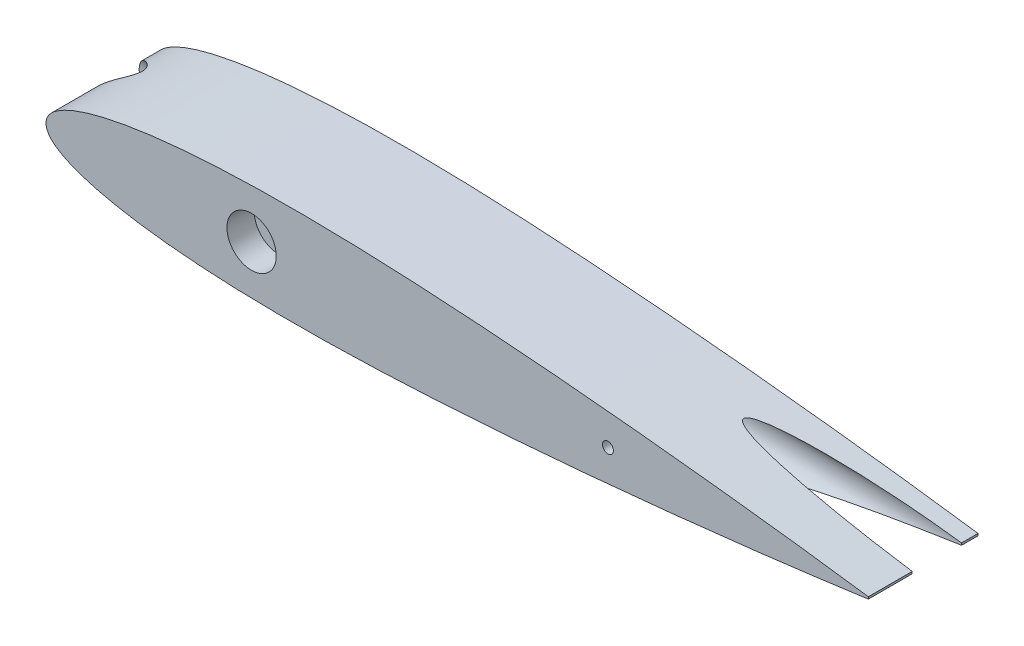
SolidWorks part; units mm, degrees
material "ABS"
ref_plane "Front Plane" through (0, 0, 0) normal (0, 0, 1) x (1, 0, 0)
ref_plane "Top Plane" through (0, 0, 0) normal (0, 1, 0) x (1, 0, 0)
ref_plane "Right Plane" through (0, 0, 0) normal (1, 0, 0) x (0, 0, -1)
sketch "Sketch5" plane through (0, 0, 0) normal (0, 0, 1) x (1, 0, 0)
  line L1 (300, 0.378) -> (300, -0.378)
  spline S1 degree 3 poles (300, 0.378) (299.2704, 0.4794) (297.2347, 0.7625) (293.6597, 1.2577) (289.1124, 1.8742) (284.0808, 2.5445) (278.752, 3.2381) (273.2659, 3.9349) (267.706, 4.629) (262.1146, 5.3131) (256.5083, 5.9822) (250.8917, 6.638) (245.2696, 7.2818) (239.6473, 7.9122) (234.0251, 8.527) (228.3991, 9.1262) (222.7683, 9.7131) (217.1359, 10.2875) (211.5054, 10.8469) (205.8776, 11.3916) (200.2515, 11.9209) (194.6264, 12.4346) (189.0028, 12.9319) (183.3815, 13.4131) (177.7632, 13.8764) (172.1483, 14.3212) (166.5375, 14.7478) (160.9317, 15.1542) (155.3317, 15.5391) (149.7375, 15.9026) (144.1487, 16.2418) (138.5657, 16.5574) (132.9909, 16.8474) (127.4274, 17.1102) (121.8776, 17.3439) (116.3408, 17.5453) (110.8155, 17.7127) (105.3013, 17.8445) (99.8006, 17.9401) (94.3174, 17.9966) (88.8558, 18.0101) (83.4186, 17.9792) (78.0085, 17.8992) (72.6285, 17.767) (67.2827, 17.5794) (61.9774, 17.3315) (56.7207, 17.021) (51.5252, 16.641) (46.4082, 16.1902) (41.3942, 15.6617) (36.5157, 15.054) (31.819, 14.3656) (27.3662, 13.6035) (23.2352, 12.7826) (19.5026, 11.9203) (16.2183, 11.0446) (13.3892, 10.1751) (10.9849, 9.3335) (8.9616, 8.5221) (7.2673, 7.747) (5.8461, 7.0106) (4.6477, 6.3006) (3.6282, 5.6065) (2.7519, 4.9266) (2.0063, 4.2499) (1.3906, 3.5703) (0.901, 2.8909) (0.5293, 2.2202) (0.2605, 1.5665) (0.0857, 0.931) (-0.0035, 0.309) (-0.0035, -0.309) (0.0857, -0.931) (0.2605, -1.5665) (0.5293, -2.2202) (0.901, -2.8909) (1.3906, -3.5703) (2.0063, -4.2499) (2.7519, -4.9266) (3.6282, -5.6065) (4.6477, -6.3006) (5.8461, -7.0106) (7.2673, -7.747) (8.9616, -8.5221) (10.9849, -9.3335) (13.3892, -10.1751) (16.2183, -11.0446) (19.5026, -11.9203) (23.2352, -12.7826) (27.3661, -13.6036) (31.8191, -14.3651) (36.5156, -15.0541) (41.3942, -15.6616) (46.4082, -16.1902) (51.5252, -16.641) (56.7207, -17.021) (61.9774, -17.3315) (67.2827, -17.5794) (72.6285, -17.767) (78.0085, -17.8992) (83.4186, -17.9792) (88.8558, -18.0101) (94.3174, -17.9966) (99.8006, -17.9401) (105.3013, -17.8445) (110.8155, -17.7127) (116.3408, -17.5453) (121.8776, -17.3439) (127.4274, -17.1102) (132.9909, -16.8474) (138.5657, -16.5574) (144.1487, -16.2418) (149.7375, -15.9026) (155.3317, -15.5391) (160.9317, -15.1542) (166.5375, -14.7478) (172.1483, -14.3212) (177.7632, -13.8764) (183.3815, -13.4131) (189.0028, -12.9319) (194.6264, -12.4346) (200.2515, -11.9209) (205.8776, -11.3916) (211.5054, -10.8469) (217.1359, -10.2875) (222.7683, -9.7131) (228.3991, -9.1262) (234.0251, -8.527) (239.6473, -7.9122) (245.2696, -7.2818) (250.8917, -6.638) (256.5083, -5.9822) (262.1146, -5.3131) (267.706, -4.629) (273.2659, -3.9349) (278.752, -3.2381) (284.0808, -2.5445) (289.1124, -1.8742) (293.6597, -1.2577) (297.2347, -0.7625) (299.2704, -0.4794) (300, -0.378) knots 0 0 0 0 0.003612 0.010079 0.017699 0.026115 0.034971 0.04405 0.053234 0.062448 0.071674 0.080921 0.090178 0.099424 0.108664 0.117912 0.12717 0.136427 0.145675 0.154916 0.164153 0.173387 0.182616 0.191838 0.201053 0.21026 0.219459 0.228647 0.237822 0.246985 0.256137 0.265279 0.274407 0.283512 0.292592 0.301646 0.310682 0.319699 0.328695 0.33766 0.346589 0.355477 0.364323 0.373122 0.381868 0.390553 0.399166 0.40769 0.416098 0.424355 0.432412 0.440205 0.447631 0.454564 0.460855 0.466413 0.471229 0.475366 0.478901 0.481915 0.484499 0.486747 0.488741 0.490543 0.492182 0.493673 0.495032 0.496279 0.497425 0.49849 0.499503 0.500497 0.50151 0.502575 0.503721 0.504968 0.506327 0.507818 0.509457 0.511259 0.513253 0.515501 0.518085 0.521099 0.524634 0.528771 0.533587 0.539145 0.545436 0.55237 0.559795 0.567588 0.575645 0.583902 0.59231 0.600834 0.609447 0.618132 0.626878 0.635677 0.644523 0.653411 0.66234 0.671305 0.680301 0.689318 0.698354 0.707408 0.716488 0.725593 0.734721 0.743863 0.753015 0.762178 0.771353 0.780541 0.78974 0.798947 0.808162 0.817384 0.826613 0.835847 0.845084 0.854325 0.863573 0.87283 0.882088 0.891336 0.900576 0.909822 0.919079 0.928326 0.937552 0.946766 0.95595 0.965029 0.973885 0.982301 0.989921 0.996388 1 1 1 1
  dimension "Tail chord" = 300
extrude "Boss-Extrude1" add sketch "Sketch5" along normal blind 40
sketch "Sketch6" plane through (0, 0, 0) normal (1, 0, 0) x (0, 0, -1)
  line L0 (0, -18.0036) -> (0, 18.0036) construction
  circle A0 centre (-15, 0) radius 9
  dimension "D1" = 15
  dimension "D2" = 18
extrude "Cut-Extrude6" cut sketch "Sketch6" against normal through all both and the other way through all
ref_plane "Plane1" through (0, 0, 40) normal (0, 0, 1) x (1, 0, 0)
sketch "Sketch7" plane through (0, 0, 40) normal (0, 0, 1) x (1, 0, 0)
  circle A0 centre (75, 0) radius 9
  circle A1 centre (205, 0) radius 2
  dimension "D3" = 18
  dimension "D4" = 4
  dimension "Tail chord qtr" = 75
  dimension "Small hole" = 130
extrude "Cut-Extrude7" cut sketch "Sketch7" against normal blind 10
curve "Curve6"
  spline degree 3 poles (298.242, -0.1932, 0) (300.4407, 0, 0) (298.242, 0.1932, 0) (296.4349, 0.5367, 0) (292.0253, 1.0976, 0) (286.5771, 1.8592, 0) (279.4156, 2.8001, 0) (270.9173, 3.8949, 0) (261.066, 5.1159, 0) (250.0071, 6.4339, 0) (237.8495, 7.8187, 0) (224.7304, 9.2395, 0) (210.7923, 10.6647, 0) (196.1883, 12.0613, 0) (181.0783, 13.3946, 0) (165.6277, 14.6278, 0) (150.0058, 15.7225, 0) (134.3834, 16.6392, 0) (118.9317, 17.3387, 0) (103.8195, 17.7845, 0) (89.2123, 17.9443, 0) (75.2698, 17.7935, 0) (62.1444, 17.3161, 0) (49.9793, 16.5075, 0) (38.907, 15.374, 0) (29.0471, 13.9333, 0) (20.5034, 12.2128, 0) (13.3641, 10.246, 0) (7.6828, 8.0707, 0) (3.4992, 5.7028, 0) (0.7348, 3.1014, 0) (-0.3264, 0, 0) (0.7348, -3.1014, 0) (3.4992, -5.7028, 0) (7.6828, -8.0707, 0) (13.3641, -10.246, 0) (20.5034, -12.2128, 0) (29.0471, -13.9333, 0) (38.907, -15.374, 0) (49.9793, -16.5075, 0) (62.1444, -17.3161, 0) (75.2698, -17.7935, 0) (89.2123, -17.9443, 0) (103.8195, -17.7845, 0) (118.9317, -17.3387, 0) (134.3834, -16.6392, 0) (150.0058, -15.7225, 0) (165.6277, -14.6278, 0) (181.0783, -13.3946, 0) (196.1883, -12.0613, 0) (210.7923, -10.6647, 0) (224.7304, -9.2395, 0) (237.8495, -7.8187, 0) (250.0071, -6.4339, 0) (261.066, -5.1159, 0) (270.9173, -3.8949, 0) (279.4156, -2.8001, 0) (286.5771, -1.8592, 0) (292.0253, -1.0976, 0) (296.4349, -0.5367, 0) (298.242, -0.1932, 0) (300.4407, 0, 0) (298.242, 0.1932, 0) knots -0.012119 -0.005412 -0.001357 0 0.001357 0.005412 0.012119 0.021403 0.033159 0.047255 0.063534 0.081814 0.101892 0.123547 0.146538 0.170613 0.195504 0.220938 0.246636 0.272314 0.297694 0.3225 0.346466 0.36934 0.390884 0.410879 0.429129 0.445462 0.459736 0.471848 0.481751 0.489494 0.495334 0.5 0.504666 0.510506 0.518249 0.528152 0.540264 0.554538 0.570871 0.589121 0.609116 0.63066 0.653534 0.6775 0.702306 0.727686 0.753364 0.779062 0.804496 0.829387 0.853462 0.876453 0.898108 0.918186 0.936466 0.952745 0.966841 0.978597 0.987881 0.994588 0.998643 1 1.001357 1.005412 1.012119 periodic
sketch "Sketch8" plane through (0, 0, 0) normal (0, 0, 1) x (1, 0, 0)
  spline S0 degree 3 poles (298.242, -0.1932) (300.4407, 0) (298.242, 0.1932) (296.4349, 0.5367) (292.0253, 1.0976) (286.5771, 1.8592) (279.4156, 2.8001) (270.9173, 3.8949) (261.066, 5.1159) (250.0071, 6.4339) (237.8495, 7.8187) (224.7304, 9.2395) (210.7923, 10.6647) (196.1883, 12.0613) (181.0783, 13.3946) (165.6277, 14.6278) (150.0058, 15.7225) (134.3834, 16.6392) (118.9317, 17.3387) (103.8195, 17.7845) (89.2123, 17.9443) (75.2698, 17.7935) (62.1444, 17.3161) (49.9793, 16.5075) (38.907, 15.374) (29.0471, 13.9333) (20.5034, 12.2128) (13.3641, 10.246) (7.6828, 8.0707) (3.4992, 5.7028) (0.7348, 3.1014) (-0.3264, 0) (0.7348, -3.1014) (3.4992, -5.7028) (7.6828, -8.0707) (13.3641, -10.246) (20.5034, -12.2128) (29.0471, -13.9333) (38.907, -15.374) (49.9793, -16.5075) (62.1444, -17.3161) (75.2698, -17.7935) (89.2123, -17.9443) (103.8195, -17.7845) (118.9317, -17.3387) (134.3834, -16.6392) (150.0058, -15.7225) (165.6277, -14.6278) (181.0783, -13.3946) (196.1883, -12.0613) (210.7923, -10.6647) (224.7304, -9.2395) (237.8495, -7.8187) (250.0071, -6.4339) (261.066, -5.1159) (270.9173, -3.8949) (279.4156, -2.8001) (286.5771, -1.8592) (292.0253, -1.0976) (296.4349, -0.5367) (298.242, -0.1932) (300.4407, 0) (298.242, 0.1932) knots -0.012119 -0.005412 -0.001357 0 0.001357 0.005412 0.012119 0.021403 0.033159 0.047255 0.063534 0.081814 0.101892 0.123547 0.146538 0.170613 0.195504 0.220938 0.246636 0.272314 0.297694 0.3225 0.346466 0.36934 0.390884 0.410879 0.429129 0.445462 0.459736 0.471848 0.481751 0.489494 0.495334 0.5 0.504666 0.510506 0.518249 0.528152 0.540264 0.554538 0.570871 0.589121 0.609116 0.63066 0.653534 0.6775 0.702306 0.727686 0.753364 0.779062 0.804496 0.829387 0.853462 0.876453 0.898108 0.918186 0.936466 0.952745 0.966841 0.978597 0.987881 0.994588 0.998643 1 1.001357 1.005412 1.012119 only from (300, 0) to (300, 0) construction
  spline S1 degree 3 poles (298.242, -0.1932) (300.4407, 0) (298.242, 0.1932) (296.4349, 0.5367) (292.0253, 1.0976) (286.5771, 1.8592) (279.4156, 2.8001) (270.9173, 3.8949) (261.066, 5.1159) (250.0071, 6.4339) (237.8495, 7.8187) (224.7304, 9.2395) (210.7923, 10.6647) (196.1883, 12.0613) (181.0783, 13.3946) (165.6277, 14.6278) (150.0058, 15.7225) (134.3834, 16.6392) (118.9317, 17.3387) (103.8195, 17.7845) (89.2123, 17.9443) (75.2698, 17.7935) (62.1444, 17.3161) (49.9793, 16.5075) (38.907, 15.374) (29.0471, 13.9333) (20.5034, 12.2128) (13.3641, 10.246) (7.6828, 8.0707) (3.4992, 5.7028) (0.7348, 3.1014) (-0.3264, 0) (0.7348, -3.1014) (3.4992, -5.7028) (7.6828, -8.0707) (13.3641, -10.246) (20.5034, -12.2128) (29.0471, -13.9333) (38.907, -15.374) (49.9793, -16.5075) (62.1444, -17.3161) (75.2698, -17.7935) (89.2123, -17.9443) (103.8195, -17.7845) (118.9317, -17.3387) (134.3834, -16.6392) (150.0058, -15.7225) (165.6277, -14.6278) (181.0783, -13.3946) (196.1883, -12.0613) (210.7923, -10.6647) (224.7304, -9.2395) (237.8495, -7.8187) (250.0071, -6.4339) (261.066, -5.1159) (270.9173, -3.8949) (279.4156, -2.8001) (286.5771, -1.8592) (292.0253, -1.0976) (296.4349, -0.5367) (298.242, -0.1932) (300.4407, 0) (298.242, 0.1932) knots -0.012119 -0.005412 -0.001357 0 0.001357 0.005412 0.012119 0.021403 0.033159 0.047255 0.063534 0.081814 0.101892 0.123547 0.146538 0.170613 0.195504 0.220938 0.246636 0.272314 0.297694 0.3225 0.346466 0.36934 0.390884 0.410879 0.429129 0.445462 0.459736 0.471848 0.481751 0.489494 0.495334 0.5 0.504666 0.510506 0.518249 0.528152 0.540264 0.554538 0.570871 0.589121 0.609116 0.63066 0.653534 0.6775 0.702306 0.727686 0.753364 0.779062 0.804496 0.829387 0.853462 0.876453 0.898108 0.918186 0.936466 0.952745 0.966841 0.978597 0.987881 0.994588 0.998643 1 1.001357 1.005412 1.012119 only from (300, 0) to (300, 0)
equation "\"Tail chord qtr@Sketch7\" = \"Tail chord@Sketch5\" * 0.25"
equation "\"Small hole@Sketch7\" = \"Tail chord qtr@Sketch7\" * 2 - 20"
equation "\"Chord\"= 300mm'Tail chord"
equation "\"Tail chord@Sketch5\"=\"Chord\""
